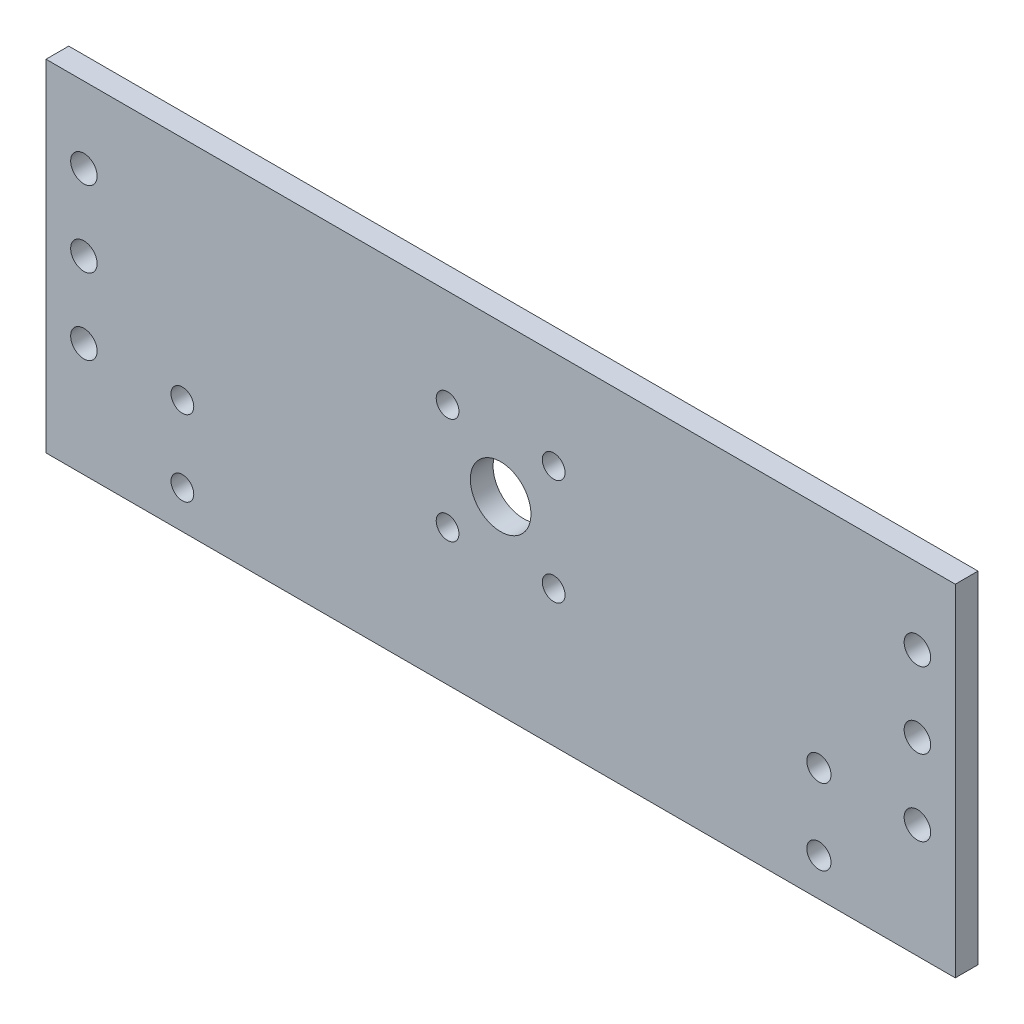
SolidWorks part; units mm, degrees
ref_plane "Plan de face" through (0, 0, 0) normal (0, 0, 1) x (1, 0, 0)
ref_plane "Plan de dessus" through (0, 0, 0) normal (0, 1, 0) x (1, 0, 0)
ref_plane "Plan de droite" through (0, 0, 0) normal (1, 0, 0) x (0, 0, -1)
sketch "Esquisse1" plane through (0, 0, 0) normal (0, 0, 1) x (1, 0, 0)
  line L1 (60, -22.5) -> (-60, -22.5)
  line L2 (60, -22.5) -> (60, 22.5)
  line L3 (60, 22.5) -> (-60, 22.5)
  line L4 (-60, -22.5) -> (-60, 22.5)
  line L5 (60, -22.5) -> (-60, 22.5) construction
  line L6 (60, 22.5) -> (-60, -22.5) construction
  point P0 (0, 0)
  dimension "D1" = 45
  dimension "D2" = 120
extrude "Boss.-Extru.1" add sketch "Esquisse1" along normal blind 3
sketch "Esquisse2" plane through (0, 0, 3) normal (0, 0, 1) x (1, 0, 0)
  line L0 (60, 22.5) -> (-60, 22.5) construction
  line L2 (-55, 12.5) -> (60, 12.5) construction
  line L3 (60, -22.5) -> (60, 22.5) construction
  line L4 (-55, 12.5) -> (-55, -22.5) construction
  line L5 (-60, -22.5) -> (60, -22.5) construction
  line L6 (-7, 9.5) -> (7, 9.5) construction
  line L7 (0, 0) -> (0, -22.5) construction
  line L8 (7, -9.5) -> (-7, -9.5) construction
  line L9 (12, -4.5) -> (12, 9.5) construction
  line L10 (7, 14.5) -> (-7, 14.5) construction
  line L11 (-12, -4.5) -> (-12, 9.5) construction
  line L12 (12, -9.5) -> (-12, 14.5) construction
  line L13 (12, 14.5) -> (-12, -9.5) construction
  line L14 (-7, 9.5) -> (-7, -4.5) construction
  line L15 (55, 12.5) -> (55, -22.5) construction
  circle A0 centre (-55, 12.5) radius 1.7476
  circle A2 centre (55, 12.5) radius 1.7476
  circle A3 centre (-55, 2.5) radius 1.7476
  circle A4 centre (-55, -7.5) radius 1.7476
  circle A12 centre (55, -7.5) radius 1.7476
  circle A13 centre (55, 2.5) radius 1.7476
  circle A15 centre (0, 2.5) radius 4
  arc A16 (7, -9.5) -> (12, -4.5) centre (7, -4.5) ccw construction
  arc A17 (-7, -9.5) -> (-12, -4.5) centre (-7, -4.5) cw construction
  arc A18 (12, 9.5) -> (7, 14.5) centre (7, 9.5) ccw construction
  arc A19 (-7, 14.5) -> (-12, 9.5) centre (-7, 9.5) ccw construction
  circle A20 centre (-7, 9.5) radius 1.5
  circle A21 centre (7, 9.5) radius 1.5
  circle A22 centre (7, -4.5) radius 1.5
  circle A23 centre (-7, -4.5) radius 1.5
  circle A25 centre (0, 12.5) radius 1.7476 [skipped]
  circle A26 centre (42, -7.5) radius 1.6
  circle A27 centre (42, -17.5) radius 1.6
  circle A28 centre (-42, -17.4659) radius 1.5
  circle A29 centre (-42, -7.4659) radius 1.5
  circle A30 centre (42, -7.5) radius 1.6 construction
  circle A31 centre (42, -17.5) radius 1.6 construction
  circle A32 centre (-42, -7.4659) radius 1.5 construction
  circle A33 centre (-42, -17.4659) radius 1.5 construction
  point P25 (42.4, -7.5)
  dimension "D7" = 14
  dimension "D8" = 8
  dimension "D10" = 5
  dimension "D12" = 3
  dimension "D1" = 10
  dimension "D2" = 15
  dimension "D4" = 5
  dimension "D6" = 14
  dimension "D9" = 10
  dimension "30" = 25
  dimension "D11" = 14
  dimension "D3" = 3
  dimension "D5" = 3
  dimension "D13" = 2
  dimension "D14" = 2
extrude "Enlèv. mat.-Extru.1" cut sketch "Esquisse2" against normal blind 10
